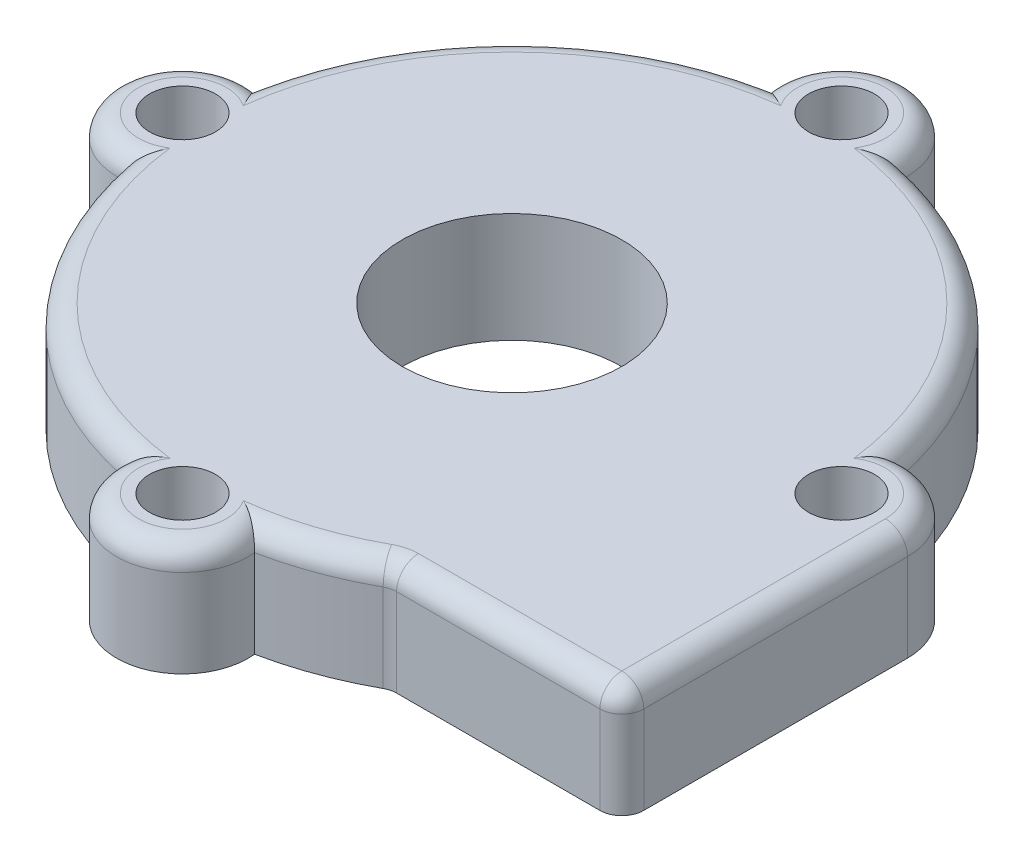
SolidWorks part; units mm, degrees
ref_plane "Front Plane" through (0, 0, 0) normal (0, 0, 1) x (1, 0, 0)
ref_plane "Top Plane" through (0, 0, 0) normal (0, 1, 0) x (1, 0, 0)
ref_plane "Right Plane" through (0, 0, 0) normal (1, 0, 0) x (0, 0, -1)
sketch "Sketch1" plane through (0, 0, 0) normal (0, 1, 0) x (1, 0, 0)
  circle A0 centre (0, 0) radius 15
  circle A1 centre (0, 0) radius 5
  dimension "D1" = 30
  dimension "D2" = 10
extrude "Boss-Extrude1" add sketch "Sketch1" along normal blind 5
sketch "Sketch3" plane through (0, 0, 0) normal (0, 1, 0) x (1, 0, 0)
  line L0 (0, -2.75) -> (0, 2.75) construction
  circle A0 centre (0, 15) radius 3
  circle A1 centre (0, 0) radius 15 construction
  dimension "D1" = 6
extrude "Boss-Extrude2" add sketch "Sketch3" along normal blind 5
sketch "Sketch4" plane through (0, 5, 0) normal (0, 1, 0) x (1, 0, 0)
  circle A0 centre (0, 15) radius 1.5
  dimension "D1" = 3
extrude "Cut-Extrude1" cut sketch "Sketch4" against normal blind 5
pattern_circular "CirPattern1" count 4 over 360 about axis through (0, 0, 0) along (0, 1, 0) of "Boss-Extrude2"
sketch "Sketch5" plane through (0, 5, 0) normal (0, 1, 0) x (1, 0, 0)
  line L0 (5.5776, -13) -> (18, -13)
  line L1 (18, -13) -> (18, 0)
  line L2 (18, 0) -> (10.2718, 0)
  line L3 (10.2718, 0) -> (5.5776, -13)
  line L4 (7.746, -13) -> (17, -13) construction
  line L5 (18, -7) -> (18, -11) construction
  arc A0 (14.7, -2.985) -> (14.7, 2.985) centre (15, 0) ccw construction
extrude "Boss-Extrude3" add sketch "Sketch5" against normal blind 5
pattern_circular "CirPattern2" count 4 over 360 about axis through (0, 0, 0) along (0, 1, 0) of "Cut-Extrude1"
fillet "Fillet1" radius 1 12 edges at (0, 5, -18) (-10.6066, 5, 10.6066) (-18, 5, 0) (5.3027, 5, 14.0314) (0, 5, 18) (10.6066, 5, -10.6066) (17.0125, 5, -2.2249) (18, 2.5, 13) (7.4833, 2.5, 13) (12.7417, 5, 13) (18, 5, 6.5) (-10.6066, 5, -10.6066)
